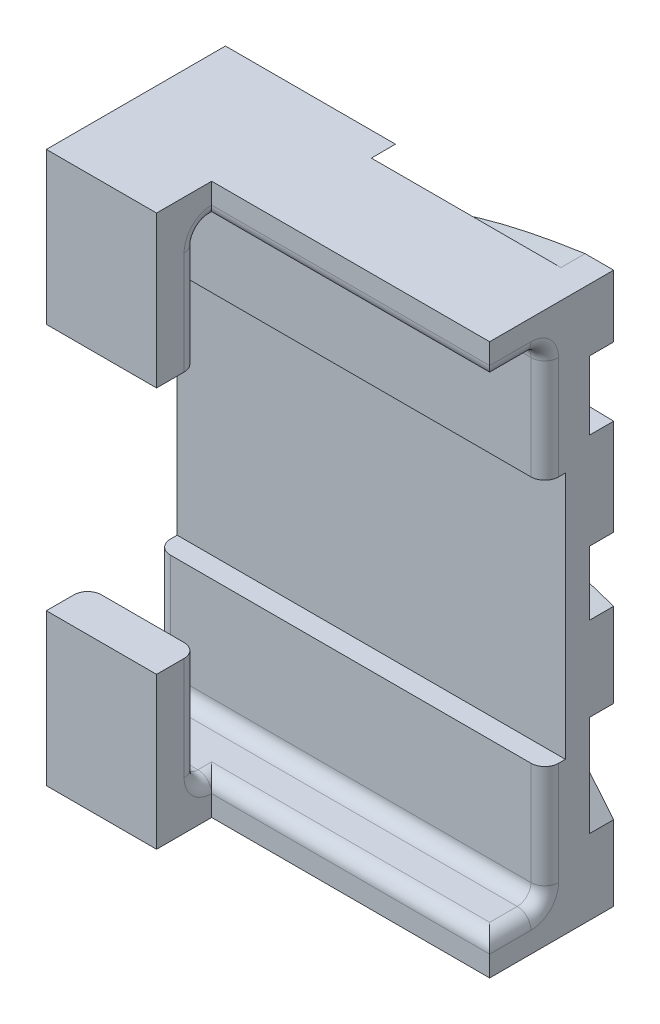
SolidWorks part; units mm, degrees
ref_plane "Front Plane" through (0, 0, 0) normal (0, 0, 1) x (1, 0, 0)
ref_plane "Top Plane" through (0, 0, 0) normal (0, 1, 0) x (1, 0, 0)
ref_plane "Right Plane" through (0, 0, 0) normal (1, 0, 0) x (0, 0, -1)
sketch "Sketch1" plane through (0, 0, 0) normal (0, 0, 1) x (1, 0, 0)
  line L1 (-14.09, -20) -> (14.09, -20)
  line L2 (-14.09, -20) -> (-14.09, 20)
  line L3 (-14.09, 20) -> (14.09, 20)
  line L4 (14.09, -20) -> (14.09, 20)
  line L5 (-14.09, -20) -> (14.09, 20) construction
  line L6 (-14.09, 20) -> (14.09, -20) construction
  point P0 (0, 0)
  dimension "D1" = 40
  dimension "D2" = 28.18
extrude "Boss-Extrude1" add sketch "Sketch1" along normal blind 11 and the other way blind 2
sketch "Sketch3" plane through (-14.09, 0, 0) normal (-1, 0, 0) x (0, 0, 1)
  line L0 (8, 9) -> (11, 9)
  line L5 (8, 17.5) -> (3, 17.5)
  line L6 (8, 17.5) -> (8, 9)
  line L7 (8, -17.5) -> (3, -17.5)
  line L8 (3, 17.5) -> (3, 9)
  line L9 (11, -9) -> (8, -9)
  line L10 (8, -9) -> (8, -17.5)
  line L13 (3, -9) -> (1.5034, -9)
  line L14 (11, 9) -> (11, -9)
  line L15 (14.8907, 0) -> (-5.9971, 0) construction
  line L16 (3, 9) -> (1.5034, 9)
  line L17 (1.5034, 9) -> (1.5034, -9)
  line L18 (3, -9) -> (3, -17.5)
  dimension "D1" = 3
  dimension "D2" = 5
  dimension "D3" = 35
extrude "Cut-Extrude1" cut sketch "Sketch3" against normal blind 37
sketch "Sketch4" plane through (0, -20, 0) normal (0, -1, 0) x (1, 0, 0)
  line L0 (-14.09, 11) -> (14.09, 11) construction
  line L1 (-6.09, 11) -> (14.09, 11)
  line L2 (-6.09, 11) -> (-6.09, 7)
  line L3 (-6.09, 7) -> (14.09, 7)
  line L4 (14.09, 11) -> (14.09, 7)
  line L5 (14.09, -2) -> (14.09, 11) construction
  line L6 (-14.09, -2) -> (-14.09, 11) construction
  dimension "D1" = 4
  dimension "D2" = 8
extrude "Cut-Extrude2" cut sketch "Sketch4" against normal blind 40
sketch "Sketch5" plane through (0, 0, -2) normal (0, 0, -1) x (-1, 0, 0)
  line L0 (14.09, 4.4317) -> (14.09, 4.2995)
  line L1 (-14.09, 20) -> (14.09, 20) construction
  line L2 (1.7471, 20) -> (-12.0158, 20)
  line L3 (14.09, 4.4317) -> (14.09, 4.2995)
  line L4 (6.9247, -20.049) -> (1.3985, -20.049)
  line L5 (-14.09, 15.483) -> (-14.09, 10.5052)
  line L6 (1.7471, 20) -> (-12.0158, 20)
  line L7 (6.9247, -20.049) -> (1.3985, -20.049)
  line L8 (-4.8324, -20.049) -> (-9.4224, -20.049)
  line L9 (-14.09, 15.483) -> (-14.09, 10.5052)
  line L10 (-14.09, 3.5233) -> (-14.09, -1.1313)
  line L11 (-14.09, -7.2405) -> (-14.09, -14.5457)
  line L12 (-4.8324, -20.049) -> (-9.4224, -20.049)
  line L13 (14.09, 20) -> (14.09, -20) construction
  spline S0 degree 3 poles (1.7471, 20) (22.5217, 10.1019) (6.4841, -5.6713) (6.9247, -20.049) knots 0 0 0 0 0.832841 0.832841 0.832841 0.832841
  spline S1 degree 3 poles (-12.0158, 20) (19.8935, 15.4318) (4.9435, -2.9122) (1.3985, -20.049) knots 0 0 0 0 0.886772 0.886772 0.886772 0.886772
  spline S2 degree 3 poles (-14.09, 15.483) (19.4581, 13.6302) (-0.2323, -3.6868) (-4.8324, -20.049) knots 0 0 0 0 0.882154 0.882154 0.882154 0.882154
  spline S3 degree 3 poles (-14.09, 10.5052) (15.4705, 11.5679) (-5.2505, -5.076) (-9.4224, -20.049) knots 0 0 0 0 0.871233 0.871233 0.871233 0.871233
  spline S4 degree 2 poles (-14.09, 3.5233) (7.9134, 11.6377) (-14.09, -14.5457) knots 0 0 0 1 1 1
  spline S5 degree 2 poles (-14.09, -1.1313) (-1.6541, 3.2119) (-14.09, -7.2405) knots 0 0 0 1 1 1
  line M1 (-14.09, 20) -> (-14.09, -20)
  line M2 (-14.09, -20) -> (14.09, -20)
  line M4 (14.09, 20) -> (-14.09, 20)
extrude "Cut-Extrude3" cut sketch "Sketch5" against normal blind 1.75 contours S3 S2 M1 M2 | S5 S4 M1 | S1 S0 M4 M2 region at (-11.5708, 2.1158, -2) region at (7.1136, -19.5966, -2) region at (4.526, -0.8216, -2)
fillet "Fillet1" radius 1 20 edges at (-14.09, -13.25, 3) (-14.09, -13.25, 8) (14.09, -13.25, 3) (-6.09, -13.25, 8) (14.09, 13.25, 3) (-14.09, 13.25, 3) (-14.09, 13.25, 8) (-6.09, 13.25, 8) (-14.09, -17.5, 5.5) (0, -17.5, 3) (14.09, -17.5, 5) (4, -17.5, 7) (-6.09, -17.5, 7.5) (-10.09, -17.5, 8) (14.09, 17.5, 5) (0, 17.5, 3) (-14.09, 17.5, 5.5) (-10.09, 17.5, 8) (-6.09, 17.5, 7.5) (4, 17.5, 7)
